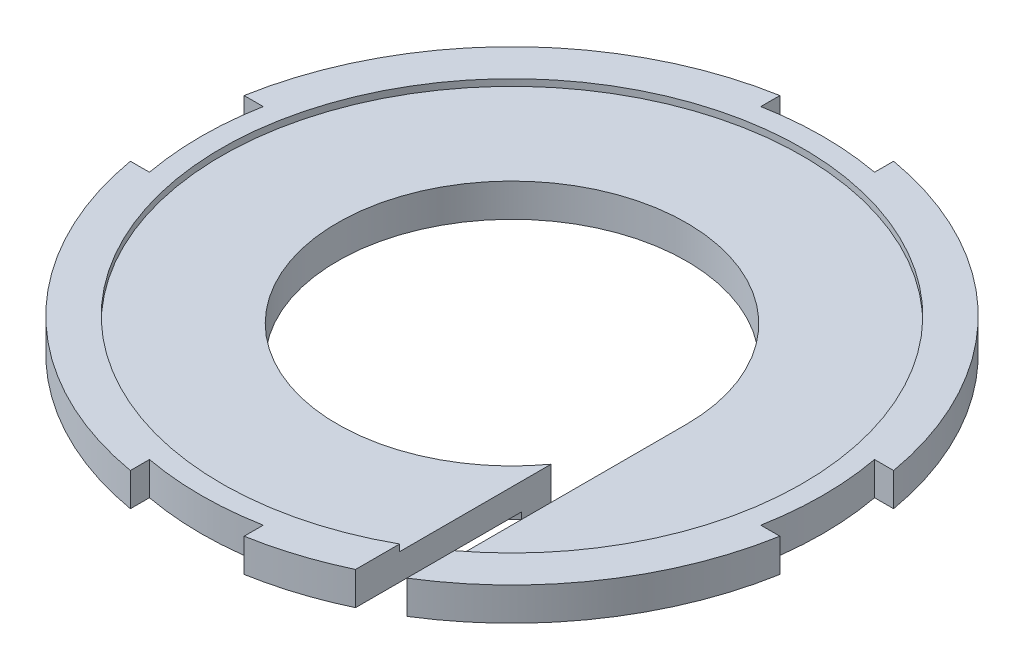
SolidWorks part; units mm, degrees
ref_plane "Front Plane" through (0, 0, 0) normal (0, 0, 1) x (1, 0, 0)
ref_plane "Top Plane" through (0, 0, 0) normal (0, 1, 0) x (1, 0, 0)
ref_plane "Right Plane" through (0, 0, 0) normal (1, 0, 0) x (0, 0, -1)
sketch "Sketch1" plane through (0, 0, 0) normal (0, 1, 0) x (1, 0, 0)
  line L0 (35.1471, 6.5405) -> (37.341, 6.5405)
  line L1 (35.1471, -6.5405) -> (37.341, -6.5405)
  line L2 (-3.4925, 0) -> (3.4925, 0) construction
  line L3 (6.5405, -35.1471) -> (6.5405, -37.341)
  line L4 (-6.5405, -35.1471) -> (-6.5405, -37.341)
  line L5 (-35.1471, -6.5405) -> (-37.341, -6.5405)
  line L6 (-35.1471, 6.5405) -> (-37.341, 6.5405)
  line L7 (-6.5405, 35.1471) -> (-6.5405, 37.341)
  line L8 (6.5405, 35.1471) -> (6.5405, 37.341)
  arc A1 (-37.341, -6.5405) -> (-6.5405, -37.341) centre (0, 0) ccw
  circle A2 centre (0, 0) radius 15.24
  arc A3 (-35.1471, 6.5405) -> (-35.1471, -6.5405) centre (0, 0) ccw
  arc A4 (6.5405, 35.1471) -> (-6.5405, 35.1471) centre (0, 0) ccw
  arc A5 (35.1471, -6.5405) -> (35.1471, 6.5405) centre (0, 0) ccw
  arc A6 (-6.5405, -35.1471) -> (6.5405, -35.1471) centre (0, 0) ccw
  arc A7 (6.5405, -37.341) -> (37.341, -6.5405) centre (0, 0) ccw
  arc A8 (37.341, 6.5405) -> (6.5405, 37.341) centre (0, 0) ccw
  arc A9 (-6.5405, 37.341) -> (-37.341, 6.5405) centre (0, 0) ccw
  point P26 (0, 0)
  dimension "D1" = 75.819
  dimension "D2" = 71.501
  dimension "D6" = 30.48
  dimension "D3" = 13.081
  dimension "D4" = 6.5405
  dimension "D5" = 4
sketch "Sketch14" plane through (0, 0, 0) normal (1, 0, 0) x (0, 0, -1)
  line L0 (35.814, 0) -> (35.814, 3.81)
  line L1 (41.0751, 0) -> (-41.0751, 0) construction
  line L3 (47.69, 2.2488) -> (48.146, 2.2488)
  dimension "D1" = 90
  dimension "D2" = 35.814
  dimension "D3" = 3.81
sweep "Sweep1" add profiles "Sketch1" path "Sketch14"
ref_axis "Axis1" through (41.0751, 0, 0) along (-1, 0, 0)
ref_plane "Plane2" through (0, 0, 0) normal (0, -0.9903, 0.1392) x (-1, 0, 0)
sketch "Sketch2" plane through (0, 0, 0) normal (0, -1, 0) x (1, 0, 0)
  line L0 (16.256, 37.2355) -> (16.256, 11.7638)
  line L1 (20.066, 0) -> (20.066, 35.3284)
  line L2 (6.917, 0) -> (-6.917, 0) construction
  arc A1 (20.066, 35.3284) -> (16.256, 37.2355) centre (0, 0) ccw
  arc A2 (16.256, 11.7638) -> (20.066, 0) centre (0, 0) ccw
  dimension "D1" = 20.066
  dimension "D2" = 3.81
  dimension "D3" = 90
extrude "Cut-Extrude1" cut sketch "Sketch2" along normal blind 3.81 from surface starting at face at (0, 3.81, 15.24)
ref_plane "Plane3" through (0, 6.2882, -0.8837) normal (0, -0.9903, 0.1392) x (-1, 0, 0)
sketch "Sketch17" plane through (0, 3.81, 0) normal (0, -1, 0) x (1, 0, 0)
  circle A0 centre (0, 0) radius 33.401
extrude "Cut-Extrude4" cut sketch "Sketch17" along normal blind 0.762
sketch "Sketch19" plane through (0, 0, 0) normal (0, -1, 0) x (1, 0, 0)
  line L0 (16.256, 11.7638) -> (16.256, 15.1556)
  line L1 (20.066, 0) -> (20.066, 9.5554)
  line L2 (20.066, 32.1634) -> (20.066, 0) construction
  line L3 (16.256, 11.7638) -> (16.256, 34.2472) construction
  arc A0 (16.256, 15.1556) -> (20.066, 9.5554) centre (0, 0) ccw
  arc A1 (16.256, 11.7638) -> (20.066, 0) centre (0, 0) ccw
  dimension "D1" = 44.45
extrude "Boss-Extrude1" add sketch "Sketch19" along normal blind 0.762
